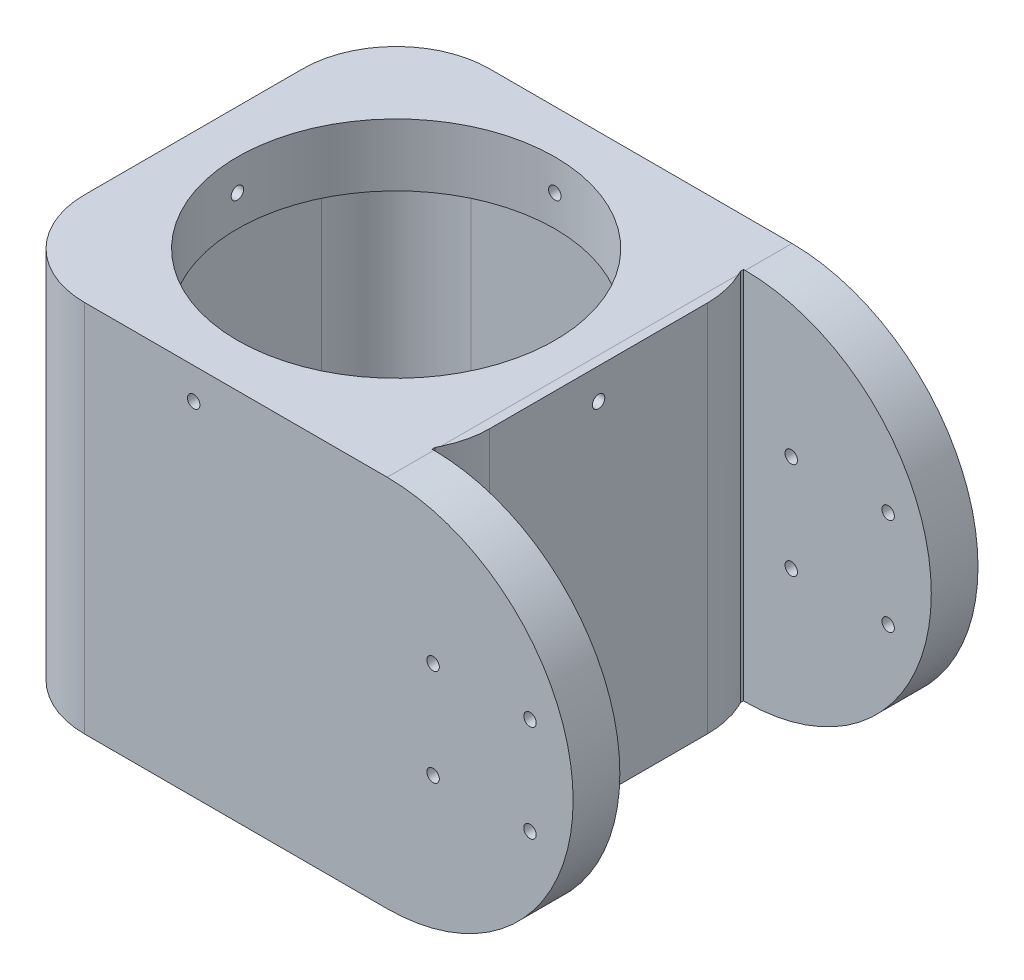
SolidWorks part; units mm, degrees
ref_plane "Front Plane" through (0, 0, 0) normal (0, 0, 1) x (1, 0, 0)
ref_plane "Top Plane" through (0, 0, 0) normal (0, 1, 0) x (1, 0, 0)
ref_plane "Right Plane" through (0, 0, 0) normal (1, 0, 0) x (0, 0, -1)
sketch "Sketch1" plane through (0, 0, 0) normal (0, 1, 0) x (1, 0, 0)
  line L2 (-17.0908, 28.818) -> (17.9092, 28.818)
  line L3 (29.9092, 16.818) -> (29.9092, -18.182)
  line L4 (-17.0908, 31.818) -> (17.9092, 31.818)
  line L5 (-32.0908, 16.818) -> (-32.0908, -18.182)
  line L6 (-17.0908, -33.182) -> (17.9092, -33.182)
  line L7 (32.9092, 16.818) -> (32.9092, -18.182)
  line L8 (-17.0908, -30.182) -> (17.9092, -30.182)
  line L9 (-29.0908, 16.818) -> (-29.0908, -18.182)
  arc A4 (17.9092, 31.818) -> (32.9092, 16.818) centre (17.9092, 16.818) cw
  arc A5 (17.9092, -33.182) -> (32.9092, -18.182) centre (17.9092, -18.182) ccw
  arc A6 (-32.0908, -18.182) -> (-17.0908, -33.182) centre (-17.0908, -18.182) ccw
  arc A7 (-17.0908, 31.818) -> (-32.0908, 16.818) centre (-17.0908, 16.818) ccw
  arc A8 (17.9092, 28.818) -> (29.9092, 16.818) centre (17.9092, 16.818) cw
  arc A9 (17.9092, -30.182) -> (29.9092, -18.182) centre (17.9092, -18.182) ccw
  arc A10 (-29.0908, -18.182) -> (-17.0908, -30.182) centre (-17.0908, -18.182) ccw
  arc A11 (-17.0908, 28.818) -> (-29.0908, 16.818) centre (-17.0908, 16.818) ccw
  point P2 (32.9092, 31.818)
  point P7 (32.9092, -33.182)
  point P14 (-32.0908, 31.818)
  dimension "D3" = 15
  dimension "D1" = 65
  dimension "D2" = 65
  dimension "D4" = 3
extrude "Boss-Extrude1" add sketch "Sketch1" along normal blind 40
sketch "Sketch2" plane through (0, 40, 0) normal (0, 1, 0) x (1, 0, 0)
  line L0 (-27.6974, 27.4246) -> (28.5158, -28.7886) construction
  line L1 (29.9092, -18.182) -> (29.9092, 16.818) construction
  line L2 (-17.0908, -30.182) -> (17.9092, -30.182) construction
  line L3 (-29.0908, 16.818) -> (-29.0908, -18.182) construction
  line L4 (17.9092, 28.818) -> (-17.0908, 28.818) construction
  line L5 (29.9092, -18.182) -> (29.9092, 16.818)
  line L6 (-17.0908, -30.182) -> (17.9092, -30.182)
  line L7 (-29.0908, 16.818) -> (-29.0908, -18.182)
  line L8 (17.9092, 28.818) -> (-17.0908, 28.818)
  line L13 (17.9092, 31.818) -> (-17.0908, 31.818)
  line L14 (-32.0908, 16.818) -> (-32.0908, -18.182)
  line L15 (-17.0908, -33.182) -> (17.9092, -33.182)
  line L16 (32.9092, -18.182) -> (32.9092, 16.818)
  line L17 (17.9092, 31.818) -> (-17.0908, 31.818)
  line L18 (-32.0908, 16.818) -> (-32.0908, -18.182)
  line L19 (-17.0908, -33.182) -> (17.9092, -33.182)
  line L20 (32.9092, -18.182) -> (32.9092, 16.818)
  arc A0 (-17.0908, 31.818) -> (-32.0908, 16.818) centre (-17.0908, 16.818) ccw construction
  arc A1 (17.9092, -33.182) -> (32.9092, -18.182) centre (17.9092, -18.182) ccw construction
  circle A2 centre (0.4092, -0.682) radius 29
  circle A3 centre (0.4092, -0.682) radius 25.5
  arc A4 (17.9092, -30.182) -> (29.9092, -18.182) centre (17.9092, -18.182) ccw construction
  arc A5 (-29.0908, -18.182) -> (-17.0908, -30.182) centre (-17.0908, -18.182) ccw construction
  arc A6 (-17.0908, 28.818) -> (-29.0908, 16.818) centre (-17.0908, 16.818) ccw construction
  arc A7 (29.9092, 16.818) -> (17.9092, 28.818) centre (17.9092, 16.818) ccw construction
  arc A8 (17.9092, -30.182) -> (29.9092, -18.182) centre (17.9092, -18.182) ccw
  arc A9 (-29.0908, -18.182) -> (-17.0908, -30.182) centre (-17.0908, -18.182) ccw
  arc A10 (-17.0908, 28.818) -> (-29.0908, 16.818) centre (-17.0908, 16.818) ccw
  arc A11 (29.9092, 16.818) -> (17.9092, 28.818) centre (17.9092, 16.818) ccw
  arc A16 (32.9092, 16.818) -> (17.9092, 31.818) centre (17.9092, 16.818) ccw
  arc A17 (-17.0908, 31.818) -> (-32.0908, 16.818) centre (-17.0908, 16.818) ccw
  arc A18 (-32.0908, -18.182) -> (-17.0908, -33.182) centre (-17.0908, -18.182) ccw
  arc A19 (17.9092, -33.182) -> (32.9092, -18.182) centre (17.9092, -18.182) ccw
  arc A20 (32.9092, 16.818) -> (17.9092, 31.818) centre (17.9092, 16.818) ccw
  arc A21 (-17.0908, 31.818) -> (-32.0908, 16.818) centre (-17.0908, 16.818) ccw
  arc A22 (-32.0908, -18.182) -> (-17.0908, -33.182) centre (-17.0908, -18.182) ccw
  arc A23 (17.9092, -33.182) -> (32.9092, -18.182) centre (17.9092, -18.182) ccw
  arc M1 (32.9092, 16.818) -> (17.9092, 31.818) centre (17.9092, 16.818) ccw
  line M2 (17.9092, 31.818) -> (-17.0908, 31.818)
  arc M3 (-17.0908, 31.818) -> (-32.0908, 16.818) centre (-17.0908, 16.818) ccw
  line M4 (-32.0908, 16.818) -> (-32.0908, -18.182)
  arc M5 (-32.0908, -18.182) -> (-17.0908, -33.182) centre (-17.0908, -18.182) ccw
  line M6 (-17.0908, -33.182) -> (17.9092, -33.182)
  arc M7 (17.9092, -33.182) -> (32.9092, -18.182) centre (17.9092, -18.182) ccw
  line M8 (32.9092, -18.182) -> (32.9092, 16.818)
  arc M9 (-29.0908, 16.818) -> (-17.0908, 28.818) centre (-17.0908, 16.818) cw
  line M10 (-17.0908, 28.818) -> (17.9092, 28.818)
  arc M11 (17.9092, 28.818) -> (29.9092, 16.818) centre (17.9092, 16.818) cw
  line M12 (29.9092, 16.818) -> (29.9092, -18.182)
  arc M13 (29.9092, -18.182) -> (17.9092, -30.182) centre (17.9092, -18.182) cw
  line M14 (17.9092, -30.182) -> (-17.0908, -30.182)
  arc M15 (-17.0908, -30.182) -> (-29.0908, -18.182) centre (-17.0908, -18.182) cw
  line M16 (-29.0908, -18.182) -> (-29.0908, 16.818)
  dimension "D1" = 58
  dimension "D2" = 51
  dimension "D3" = 0
extrude "Boss-Extrude2" add sketch "Sketch2" along normal blind 20 contours L0 A21 A8 M4 M5 M6 M7 M14 M15 M16 M9 | L0 A2 A3 | L0 A8 A2 M9 M16 M15 M14 | A10 L0 A2 M13 M12 M11 M10 | A2 L0 A3 | L0 A10 A23 M3 M10 M11 M12 M13 M8 M1 M2 region at (-22.5031, 40, -29.8844) region at (-27.2428, 40, -25.7579) region at (-21.3827, 40, -27.1796) region at (-23.3914, 40, -22.0089) region at (11.2391, 40, -25.4637) region at (-19.3545, 40, -18.0916)
sketch "Sketch3" plane through (0, 0, 33.182) normal (0, 0, 1) x (1, 0, 0)
  line L0 (0.4092, 60) -> (0.4092, 0) construction
  line L1 (-17.0908, 60) -> (17.9092, 60) construction
  line L2 (-17.0908, 0) -> (17.9092, 0) construction
  circle A0 centre (0.4092, 30) radius 4
  dimension "D1" = 8
extrude "Cut-Extrude1" cut sketch "Sketch3" against normal blind 20
sketch "Sketch5" plane through (0, 0, 33.182) normal (0, 0, 1) x (1, 0, 0)
  circle A0 centre (0.4092, 30) radius 4
  circle A1 centre (8.1874, 22.2218) radius 1.5
  circle A2 centre (-7.369, 37.7782) radius 1.5
  circle A3 centre (8.1874, 37.7782) radius 1.5
  circle A4 centre (-7.369, 22.2218) radius 1.5
  circle A6 centre (0.4092, 30) radius 4
extrude "Cut-Extrude4" cut sketch "Sketch5" against normal blind 13.5 contours A1 | A3 | A2 | A4 region at (8.1874, 22.2218, 33.182) region at (-7.369, 37.7782, 33.182) region at (8.1874, 37.7782, 33.182) region at (-7.369, 22.2218, 33.182)
sketch "Sketch6" plane through (0, 40, 0) normal (0, -1, 0) x (1, 0, 0)
  line L4 (-17.0908, -28.818) -> (17.9092, -28.818)
  line L5 (29.9092, -16.818) -> (29.9092, 18.182)
  line L6 (17.9092, 30.182) -> (-17.0908, 30.182)
  line L7 (-29.0908, 18.182) -> (-29.0908, -16.818)
  line L8 (-17.0908, -28.818) -> (17.9092, -28.818)
  line L9 (29.9092, -16.818) -> (29.9092, 18.182)
  line L10 (17.9092, 30.182) -> (-17.0908, 30.182)
  line L11 (-29.0908, 18.182) -> (-29.0908, -16.818)
  arc A4 (-29.0908, -16.818) -> (-17.0908, -28.818) centre (-17.0908, -16.818) ccw
  arc A5 (17.9092, -28.818) -> (29.9092, -16.818) centre (17.9092, -16.818) ccw
  arc A6 (29.9092, 18.182) -> (17.9092, 30.182) centre (17.9092, 18.182) ccw
  arc A7 (-17.0908, 30.182) -> (-29.0908, 18.182) centre (-17.0908, 18.182) ccw
  arc A8 (-29.0908, -16.818) -> (-17.0908, -28.818) centre (-17.0908, -16.818) ccw
  arc A9 (17.9092, -28.818) -> (29.9092, -16.818) centre (17.9092, -16.818) ccw
  arc A10 (29.9092, 18.182) -> (17.9092, 30.182) centre (17.9092, 18.182) ccw
  arc A11 (-17.0908, 30.182) -> (-29.0908, 18.182) centre (-17.0908, 18.182) ccw
  dimension "D1" = 0
extrude "Cut-Extrude5" cut sketch "Sketch6" against normal blind 3
sketch "Sketch7" plane through (0, 0, 0) normal (0, -1, 0) x (1, 0, 0)
  line L0 (61.324, 33.182) -> (17.9092, 33.182)
  line L2 (31.1757, 25.182) -> (61.324, 25.182)
  line L3 (61.324, 25.182) -> (61.324, 33.182)
  line L7 (32.9092, -16.818) -> (32.9092, 18.182)
  line L8 (17.9092, 33.182) -> (-17.0908, 33.182)
  line L9 (-32.0908, 18.182) -> (-32.0908, -16.818)
  line L10 (-17.0908, -31.818) -> (17.9092, -31.818)
  line L11 (32.9092, -16.818) -> (32.9092, 18.182)
  line L12 (17.9092, 33.182) -> (-17.0908, 33.182)
  line L13 (-32.0908, 18.182) -> (-32.0908, -16.818)
  line L14 (-17.0908, -31.818) -> (17.9092, -31.818)
  arc A0 (32.9092, 18.182) -> (17.9092, 33.182) centre (17.9092, 18.182) ccw construction
  arc A1 (32.9092, 18.182) -> (17.9092, 33.182) centre (17.9092, 18.182) ccw
  arc A5 (17.9092, -31.818) -> (32.9092, -16.818) centre (17.9092, -16.818) ccw
  arc A6 (32.9092, 18.182) -> (17.9092, 33.182) centre (17.9092, 18.182) ccw
  arc A7 (-17.0908, 33.182) -> (-32.0908, 18.182) centre (-17.0908, 18.182) ccw
  arc A8 (-32.0908, -16.818) -> (-17.0908, -31.818) centre (-17.0908, -16.818) ccw
  arc A9 (17.9092, -31.818) -> (32.9092, -16.818) centre (17.9092, -16.818) ccw
  arc A10 (32.9092, 18.182) -> (31.1757, 25.182) centre (17.9092, 18.182) ccw
  arc A11 (-17.0908, 33.182) -> (-32.0908, 18.182) centre (-17.0908, 18.182) ccw
  arc A12 (-32.0908, -16.818) -> (-17.0908, -31.818) centre (-17.0908, -16.818) ccw
  arc M12 (32.9092, 18.182) -> (17.9092, 33.182) centre (17.9092, 18.182) ccw
  dimension "D1" = 8
  dimension "D2" = 0
extrude "Boss-Extrude3" add sketch "Sketch7" against normal up to surface (60 mm away) contours L2 L3 L0 M12 region at (44.2096, 0, 29.3806) up to face at (0.4092, 60, 26.182)
sketch "Sketch8" plane through (0, 0, 33.182) normal (0, 0, 1) x (1, 0, 0)
  line L0 (31.1757, 60) -> (31.1757, 0) construction
  line L1 (31.1757, 60) -> (31.1757, 0)
  line L6 (-17.0908, 0) -> (61.324, 0)
  line L7 (61.324, 0) -> (61.324, 60)
  line L8 (61.324, 60) -> (-17.0908, 60)
  line L9 (-17.0908, 60) -> (-17.0908, 0)
  line L10 (-17.0908, 0) -> (61.324, 0)
  line L11 (61.324, 0) -> (61.324, 60)
  line L12 (61.324, 60) -> (-17.0908, 60)
  line L13 (-17.0908, 60) -> (-17.0908, 0)
  arc A0 (31.1757, 0) -> (31.1757, 60) centre (31.3236, 30) ccw
  line M11 (61.324, 0) -> (61.324, 60)
  line M12 (61.324, 60) -> (-17.0908, 60)
  dimension "D1" = 0
extrude "Cut-Extrude6" cut sketch "Sketch8" against normal blind 60 contours A0 L10 M11 | A0 L11 M12 region at (54.6233, 53.2989, 33.182) region at (54.6233, 6.7011, 33.182)
sketch "Sketch9" plane through (0, 0, 33.182) normal (0, 0, 1) x (1, 0, 0)
  line L0 (0.4092, 30) -> (42.6168, 30) construction
  line L1 (50.6168, 30) -> (61.324, 30) construction
  arc A0 (31.4716, 0) -> (31.4716, 60) centre (31.3236, 30) ccw construction
  circle A2 centre (54.395, 22.2218) radius 1.5
  circle A3 centre (38.8386, 37.7782) radius 1.5
  circle A4 centre (54.395, 37.7782) radius 1.5
  circle A5 centre (38.8386, 22.2218) radius 1.5
extrude "Cut-Extrude7" cut sketch "Sketch9" against normal blind 60
sketch "Sketch11" plane through (0, 60, 0) normal (0, 1, 0) x (1, 0, 0)
  line L0 (17.9092, 31.818) -> (57.9378, 31.818)
  line L1 (31.1757, 23.818) -> (58.6825, 23.818)
  line L2 (61.324, -25.182) -> (61.324, 34.534) construction
  line L3 (57.9378, 31.818) -> (61.324, 31.818)
  line L4 (61.324, 31.818) -> (61.324, 23.818)
  line L5 (61.324, 23.818) -> (58.6825, 23.818)
  arc A0 (31.4716, 23.226) -> (17.9092, 31.818) centre (17.9092, 16.818) ccw construction
  arc A1 (31.4716, 23.226) -> (17.9092, 31.818) centre (17.9092, 16.818) ccw
  arc M9 (31.4716, 23.226) -> (17.9092, 31.818) centre (17.9092, 16.818) ccw
  dimension "D1" = 8
extrude "Boss-Extrude4" add sketch "Sketch11" against normal up to surface (60 mm away) contours L5 L4 L3 L0 L1 M9 region at (44.2096, 60, -28.0167) up to face at (0.4092, 0, 0.682)
sketch "Sketch12" plane through (0, 0, -31.818) normal (0, 0, -1) x (-1, 0, 0)
  line L4 (-61.324, 0) -> (17.0908, 0)
  line L5 (17.0908, 0) -> (17.0908, 60)
  line L6 (17.0908, 60) -> (-61.324, 60)
  line L7 (-61.324, 60) -> (-61.324, 0)
  line L8 (-61.324, 0) -> (17.0908, 0)
  line L9 (17.0908, 0) -> (17.0908, 60)
  line L10 (17.0908, 60) -> (-61.324, 60)
  line L11 (-61.324, 60) -> (-61.324, 0)
  arc A0 (-31.4716, 60) -> (-31.4716, 0) centre (-31.3236, 30) ccw construction
  circle A1 centre (-54.395, 37.7782) radius 1.5 construction
  circle A2 centre (-54.395, 22.2218) radius 1.5 construction
  circle A3 centre (-38.8386, 22.2218) radius 1.5 construction
  circle A4 centre (-38.8386, 37.7782) radius 1.5 construction
  arc A6 (-31.4716, 60) -> (-31.4716, 0) centre (-31.3236, 30) ccw
  circle A7 centre (-54.395, 37.7782) radius 1.5
  circle A8 centre (-54.395, 22.2218) radius 1.5
  circle A9 centre (-38.8386, 22.2218) radius 1.5
  circle A10 centre (-38.8386, 37.7782) radius 1.5
  line M5 (-61.324, 0) -> (17.0908, 0)
  line M8 (-61.324, 60) -> (-61.324, 0)
  dimension "D1" = 0
extrude "Cut-Extrude8" cut sketch "Sketch12" against normal up to surface (8 mm away) contours A6 L10 M8 | A6 L11 M5 | A9 | A10 | A8 | A7 region at (54.6233, 6.7011, -31.818) region at (54.6233, 53.2989, -31.818) region at (54.395, 37.7782, -31.818) region at (54.395, 22.2218, -31.818) region at (38.8386, 22.2218, -31.818) region at (38.8386, 37.7782, -31.818) up to face at (46.2498, 30, -23.818)
sketch "Sketch13" plane through (0, 0, 25.182) normal (0, 0, -1) x (-1, 0, 0)
  line L3 (-31.1757, 60) -> (-31.4716, 60)
  line L4 (-31.4716, 0) -> (-31.1757, 0)
  line L5 (-31.1757, 0) -> (-31.1757, 60)
  line L6 (-31.1757, 60) -> (-31.4716, 60)
  line L7 (-31.4716, 0) -> (-31.1757, 0)
  line L8 (-31.1757, 0) -> (-31.1757, 60)
  arc A1 (-31.4716, 60) -> (-31.4716, 0) centre (-31.3236, 30) ccw
  arc A2 (-31.4716, 60) -> (-31.4716, 0) centre (-31.3236, 30) ccw
  dimension "D1" = 0
extrude "Cut-Extrude9" cut sketch "Sketch13" against normal blind 0.5
sketch "Sketch14" plane through (0, 0, -23.818) normal (0, 0, 1) x (1, 0, 0)
  line L3 (31.1757, 0) -> (31.4716, 0)
  line L4 (31.4716, 60) -> (31.1757, 60)
  line L5 (31.1757, 60) -> (31.1757, 0)
  line L6 (31.1757, 0) -> (31.4716, 0)
  line L7 (31.4716, 60) -> (31.1757, 60)
  line L8 (31.1757, 60) -> (31.1757, 0)
  arc A1 (31.4716, 0) -> (31.4716, 60) centre (31.3236, 30) ccw
  arc A2 (31.4716, 0) -> (31.4716, 60) centre (31.3236, 30) ccw
  dimension "D1" = 0
extrude "Cut-Extrude10" cut sketch "Sketch14" against normal blind 0.5
sketch "Sketch15" plane through (0, 0, 33.182) normal (0, 0, 1) x (1, 0, 0)
  circle A0 centre (0.4092, 30) radius 4 construction
  circle A1 centre (-7.369, 22.2218) radius 1.5 construction
  circle A2 centre (8.1874, 22.2218) radius 1.5 construction
  circle A3 centre (8.1874, 37.7782) radius 1.5 construction
  circle A4 centre (-7.369, 37.7782) radius 1.5 construction
  circle A5 centre (0.4092, 30) radius 4
  circle A6 centre (-7.369, 22.2218) radius 1.5
  circle A7 centre (8.1874, 22.2218) radius 1.5
  circle A8 centre (8.1874, 37.7782) radius 1.5
  circle A9 centre (-7.369, 37.7782) radius 1.5
extrude "Boss-Extrude5" add sketch "Sketch15" against normal up to surface (3 mm away) up to face at (-8.869, 22.2218, 30.182)
sketch "Sketch16" plane through (0, 43, 0) normal (0, -1, 0) x (1, 0, 0)
  line L0 (17.9092, 18.6342) -> (26.3945, 26.6673) construction
  line L4 (-17.0908, -28.818) -> (17.9092, -28.818)
  line L5 (29.9092, -16.818) -> (29.9092, 18.182)
  line L6 (17.9092, 30.182) -> (-17.0908, 30.182)
  line L7 (-29.0908, 18.182) -> (-29.0908, -16.818)
  line L9 (29.9092, -16.818) -> (29.9092, 18.182)
  line L11 (-29.0908, 18.182) -> (-29.0908, -16.818)
  circle A0 centre (22.1518, 22.6507) radius 1
  circle A3 centre (-21.5595, 22.4246) radius 1
  arc A4 (-29.0908, -16.818) -> (-17.0908, -28.818) centre (-17.0908, -16.818) ccw
  arc A5 (17.9092, -28.818) -> (29.9092, -16.818) centre (17.9092, -16.818) ccw
  arc A6 (29.9092, 18.182) -> (17.9092, 30.182) centre (17.9092, 18.182) ccw
  arc A7 (-17.0908, 30.182) -> (-29.0908, 18.182) centre (-17.0908, 18.182) ccw
  arc A8 (-29.0908, -16.818) -> (-17.0908, -28.818) centre (-17.0908, -16.818) ccw
  arc A9 (17.9092, -28.818) -> (29.9092, -16.818) centre (17.9092, -16.818) ccw
  arc A10 (29.9092, 18.182) -> (17.9092, 30.182) centre (17.9092, 18.182) ccw
  arc A11 (-17.0908, 30.182) -> (-29.0908, 18.182) centre (-17.0908, 18.182) ccw
  circle A12 centre (-21.3335, -21.2868) radius 1
  circle A13 centre (22.3779, -21.0607) radius 1
  point P28 (0.4092, 0.682)
  dimension "D2" = 2
  dimension "D1" = 0
  dimension "D3" = 4
extrude "Cut-Extrude11" cut sketch "Sketch16" against normal blind 117 contours A13 | A12 | A3 | L0 A0 | A0 L0 region at (21.86, 43, 22.9589) region at (22.4436, 43, 22.3425) region at (-21.5595, 43, 22.4246) region at (-21.3335, 43, -21.2868) region at (22.3779, 43, -21.0607)
sketch "Sketch19" plane through (0, 43, 0) normal (0, -1, 0) x (1, 0, 0)
  arc A1 (17.9092, 30.182) -> (29.9092, 18.182) centre (26.5108, 26.7836) ccw
  arc A2 (29.9092, 18.182) -> (17.9092, 30.182) centre (17.9092, 18.182) ccw construction
  arc A3 (29.9092, 18.182) -> (17.9092, 30.182) centre (17.9092, 18.182) ccw
  arc A6 (29.9092, -16.818) -> (17.9092, -28.818) centre (26.5108, -25.4196) ccw
  arc A7 (17.9092, -28.818) -> (29.9092, -16.818) centre (17.9092, -16.818) ccw
  arc A8 (-17.0908, -28.818) -> (-29.0908, -16.818) centre (-25.6924, -25.4196) ccw
  arc A9 (-29.0908, -16.818) -> (-17.0908, -28.818) centre (-17.0908, -16.818) ccw
  arc A10 (-29.0908, 18.182) -> (-17.0908, 30.182) centre (-25.6924, 26.7836) ccw
  arc A11 (-17.0908, 30.182) -> (-29.0908, 18.182) centre (-17.0908, 18.182) ccw
  circle A12 centre (22.3779, -21.0607) radius 1 construction
  circle A13 centre (-21.3335, -21.2868) radius 1 construction
  circle A14 centre (-21.5595, 22.4246) radius 1 construction
  circle A15 centre (22.3779, -21.0607) radius 1
  circle A16 centre (-21.3335, -21.2868) radius 1
  circle A17 centre (-21.5595, 22.4246) radius 1
  circle A18 centre (22.1518, 22.6507) radius 1 construction
  circle A19 centre (22.1518, 22.6507) radius 1
  point P22 (0.4092, 0.682)
  dimension "D1" = 4
extrude "Boss-Extrude7" add sketch "Sketch19" along normal up to surface (43 mm away) up to face at (14.9259, 0, 0.682)
ref_plane "Plane1" through (0, 10, 0) normal (0, -1, 0) x (-1, 0, 0)
sketch "Sketch21" plane through (0, 10, 0) normal (0, -1, 0) x (-1, 0, 0)
  arc A0 (-29.9092, 16.818) -> (-17.9092, 28.818) centre (-17.9092, 16.818) cw
  arc A1 (-29.9092, 16.818) -> (-17.9092, 28.818) centre (-26.5108, 25.4196) ccw construction
  arc A2 (-29.9092, 16.818) -> (-17.9092, 28.818) centre (-26.5108, 25.4196) ccw
  circle A3 centre (-0.4092, -0.682) radius 25.5 construction
  circle A4 centre (-0.4092, -0.682) radius 25.5
  arc A5 (17.0908, 28.818) -> (29.0908, 16.818) centre (25.6924, 25.4196) ccw construction
  arc A6 (29.0908, -18.182) -> (17.0908, -30.182) centre (25.6924, -26.7836) ccw construction
  arc A7 (-17.9092, -30.182) -> (-29.9092, -18.182) centre (-26.5108, -26.7836) ccw construction
  arc A8 (17.0908, 28.818) -> (29.0908, 16.818) centre (25.6924, 25.4196) ccw
  arc A9 (29.0908, -18.182) -> (17.0908, -30.182) centre (25.6924, -26.7836) ccw
  arc A10 (-17.9092, -30.182) -> (-29.9092, -18.182) centre (-26.5108, -26.7836) ccw
  arc A11 (-29.9092, -18.182) -> (-17.9092, -30.182) centre (-17.9092, -18.182) ccw
  arc A12 (17.0908, -30.182) -> (29.0908, -18.182) centre (17.0908, -18.182) ccw
  arc A13 (17.0908, 28.818) -> (29.0908, 16.818) centre (17.0908, 16.818) cw
extrude "Cut-Extrude12" cut sketch "Sketch21" against normal up to surface (33 mm away) up to face at (0.4092, 43, -24.818)
sketch "Sketch23" plane through (0, 43, 0) normal (0, -1, 0) x (1, 0, 0)
  line L4 (17.9092, 30.182) -> (-17.0908, 30.182)
  line L5 (-29.0908, 18.182) -> (-29.0908, -16.818)
  line L6 (-17.0908, -28.818) -> (17.9092, -28.818)
  line L7 (29.9092, -16.818) -> (29.9092, 18.182)
  line L8 (17.9092, 30.182) -> (-17.0908, 30.182)
  line L9 (-29.0908, 18.182) -> (-29.0908, -16.818)
  line L10 (-17.0908, -28.818) -> (17.9092, -28.818)
  line L11 (29.9092, -16.818) -> (29.9092, 18.182)
  arc A4 (-17.0908, 30.182) -> (-29.0908, 18.182) centre (-17.0908, 18.182) ccw
  arc A5 (-29.0908, -16.818) -> (-17.0908, -28.818) centre (-17.0908, -16.818) ccw
  arc A6 (17.9092, -28.818) -> (29.9092, -16.818) centre (17.9092, -16.818) ccw
  arc A7 (29.9092, 18.182) -> (17.9092, 30.182) centre (17.9092, 18.182) ccw
  arc A8 (-17.0908, 30.182) -> (-29.0908, 18.182) centre (-17.0908, 18.182) ccw
  arc A9 (-29.0908, -16.818) -> (-17.0908, -28.818) centre (-17.0908, -16.818) ccw
  arc A10 (17.9092, -28.818) -> (29.9092, -16.818) centre (17.9092, -16.818) ccw
  arc A11 (29.9092, 18.182) -> (17.9092, 30.182) centre (17.9092, 18.182) ccw
  dimension "D1" = 0
extrude "Cut-Extrude13" cut sketch "Sketch23" against normal blind 7
sketch "Sketch24" plane through (0, 0, 33.182) normal (0, 0, 1) x (1, 0, 0)
  line L0 (25.9092, 60) -> (-25.0908, 60) construction
  line L1 (25.9092, 60) -> (-25.0908, 60)
  line L2 (-25.0908, 50) -> (25.9092, 50) construction
  line L3 (-25.0908, 50) -> (25.9092, 50)
  line L4 (0.4092, 50) -> (0.4092, 60) construction
  circle A0 centre (0.4092, 55) radius 1
  dimension "D1" = 2
extrude "Cut-Extrude14" cut sketch "Sketch24" against normal blind 100 and the other way blind 10 contours A0 L4 | L4 A0 region at (-0.0152, 55, 33.182) region at (0.8336, 55, 33.182)
sketch "Sketch25" plane through (32.9092, 0, 0) normal (1, 0, 0) x (0, 0, -1)
  line L0 (24.818, 60) -> (-26.182, 60) construction
  line L1 (24.818, 60) -> (-26.182, 60)
  line L2 (-26.182, 50) -> (24.818, 50) construction
  line L3 (-26.182, 50) -> (24.818, 50)
  line L4 (-0.682, 50) -> (-0.682, 60) construction
  circle A0 centre (-0.682, 55) radius 1
  dimension "D1" = 2
extrude "Cut-Extrude15" cut sketch "Sketch25" against normal blind 100 and the other way blind 100 contours L4 A0 | A0 L4 region at (32.9092, 55, 1.1064) region at (32.9092, 55, 0.2576)
sketch "Sketch28" plane through (0, 0, 0) normal (0, -1, 0) x (1, 0, 0)
  circle A0 centre (22.3779, -21.0607) radius 1 construction
  circle A1 centre (22.3779, -21.0607) radius 1
sketch "Sketch29" plane through (0, 50, 0) normal (0, -1, 0) x (1, 0, 0)
  line L4 (17.9092, 30.182) -> (-17.0908, 30.182)
  line L5 (-29.0908, 18.182) -> (-29.0908, -16.818)
  line L6 (-17.0908, -28.818) -> (17.9092, -28.818)
  line L7 (29.9092, -16.818) -> (29.9092, 18.182)
  line L8 (17.9092, 30.182) -> (-17.0908, 30.182)
  line L10 (-17.0908, -28.818) -> (17.9092, -28.818)
  circle A2 centre (22.3779, -21.0607) radius 1 construction
  circle A3 centre (-21.3335, -21.2868) radius 1 construction
  circle A4 centre (-21.5595, 22.4246) radius 1 construction
  circle A5 centre (22.1518, 22.6507) radius 1 construction
  arc A6 (29.9092, 18.182) -> (17.9092, 30.182) centre (17.9092, 18.182) ccw
  arc A7 (-17.0908, 30.182) -> (-29.0908, 18.182) centre (-17.0908, 18.182) ccw
  arc A8 (-29.0908, -16.818) -> (-17.0908, -28.818) centre (-17.0908, -16.818) ccw
  arc A9 (17.9092, -28.818) -> (29.9092, -16.818) centre (17.9092, -16.818) ccw
  arc A10 (29.9092, 18.182) -> (17.9092, 30.182) centre (17.9092, 18.182) ccw
  arc A11 (-17.0908, 30.182) -> (-29.0908, 18.182) centre (-17.0908, 18.182) ccw
  arc A12 (-29.0908, -16.818) -> (-17.0908, -28.818) centre (-17.0908, -16.818) ccw
  arc A13 (17.9092, -28.818) -> (29.9092, -16.818) centre (17.9092, -16.818) ccw
  circle A14 centre (22.3779, -21.0607) radius 1
  circle A15 centre (-21.3335, -21.2868) radius 1
  circle A16 centre (-21.5595, 22.4246) radius 1
  circle A17 centre (22.1518, 22.6507) radius 1
  circle A18 centre (22.3779, -21.0607) radius 1
  circle M18 centre (22.1518, 22.6507) radius 1
  circle M19 centre (-21.5595, 22.4246) radius 1
  circle M20 centre (-21.3335, -21.2868) radius 1
  circle M21 centre (22.3779, -21.0607) radius 1
  dimension "D1" = 0
extrude "Boss-Extrude9" add sketch "Sketch29" against normal up to surface (10 mm away) contours M18 | M19 | M20 | M21 region at (22.3779, 50, -21.0607) region at (-21.3335, 50, -21.2868) region at (-21.5595, 50, 22.4246) region at (22.1518, 50, 22.6507) up to face at (22.1518, 60, 23.6507)
sketch "Sketch30" plane through (0, 0, -31.818) normal (0, 0, -1) x (-1, 0, 0)
  circle A0 centre (-54.395, 37.7782) radius 1
  circle A1 centre (-54.395, 22.2218) radius 1
  circle A2 centre (-38.8386, 22.2218) radius 1
  circle A3 centre (-38.8386, 37.7782) radius 1
  circle A4 centre (-54.395, 22.2218) radius 1.5 construction
  circle A5 centre (-38.8386, 37.7782) radius 1.5 construction
  circle A6 centre (-54.395, 37.7782) radius 1.5 construction
  circle A7 centre (-54.395, 22.2218) radius 1.5
  circle A8 centre (-38.8386, 37.7782) radius 1.5
  circle A9 centre (-54.395, 37.7782) radius 1.5
  circle A10 centre (-38.8386, 22.2218) radius 1.5 construction
  circle A11 centre (-38.8386, 22.2218) radius 1.5
  dimension "D1" = 2
extrude "Boss-Extrude10" add sketch "Sketch30" against normal up to surface (7.5 mm away) up to face at (38.7867, 30, -24.318)
sketch "Sketch34" plane through (0, 0, 33.182) normal (0, 0, 1) x (1, 0, 0)
  circle A0 centre (54.395, 22.2218) radius 1.5 construction
  circle A1 centre (54.395, 22.2218) radius 1 construction
  circle A2 centre (38.8386, 22.2218) radius 1.5 construction
  circle A3 centre (38.8386, 22.2218) radius 1 construction
  circle A4 centre (38.8386, 37.7782) radius 1.5 construction
  circle A5 centre (38.8386, 37.7782) radius 1 construction
  circle A6 centre (54.395, 37.7782) radius 1.5 construction
  circle A7 centre (54.395, 37.7782) radius 1 construction
  circle A8 centre (54.395, 22.2218) radius 1.5
  circle A9 centre (54.395, 22.2218) radius 1
  circle A10 centre (38.8386, 22.2218) radius 1.5
  circle A11 centre (38.8386, 22.2218) radius 1
  circle A12 centre (38.8386, 37.7782) radius 1.5
  circle A13 centre (38.8386, 37.7782) radius 1
  circle A14 centre (54.395, 37.7782) radius 1.5
  circle A15 centre (54.395, 37.7782) radius 1
extrude "Boss-Extrude12" add sketch "Sketch34" against normal up to surface (7.5 mm away) up to face at (38.7867, 30, 25.682)
